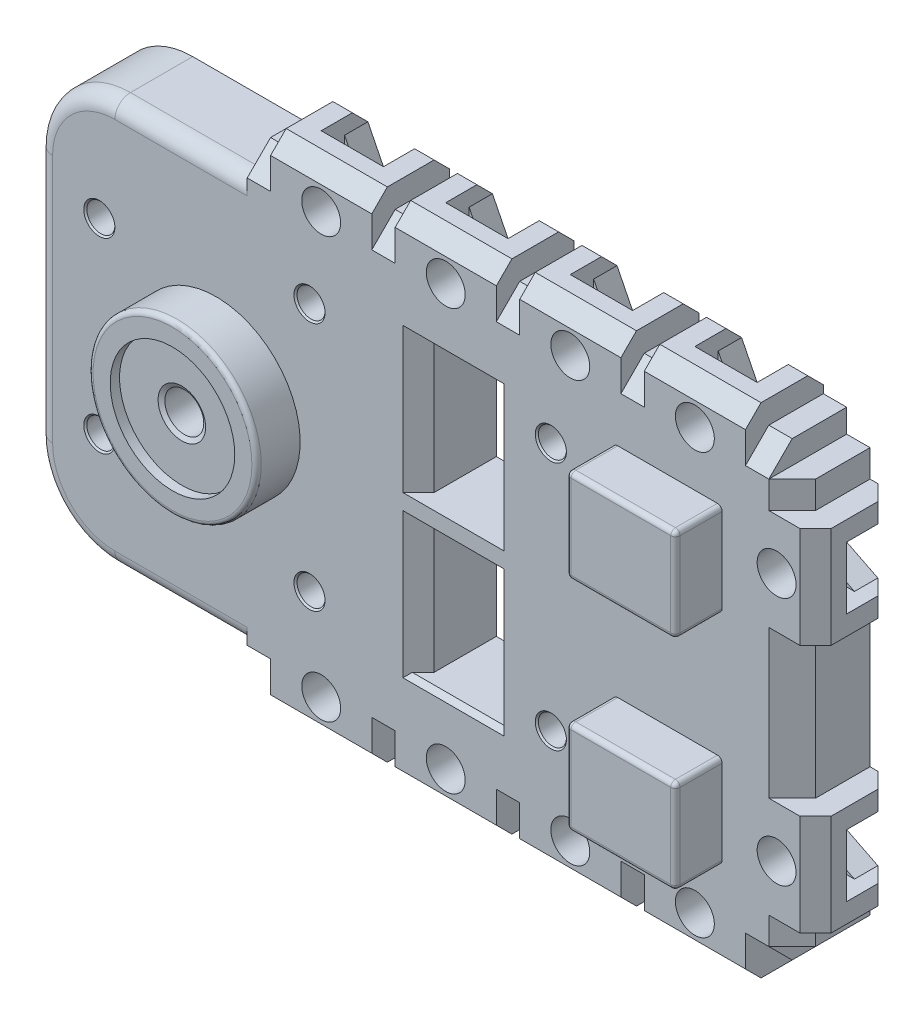
SolidWorks part; units mm, degrees
ref_plane "Front" through (0, 0, 0) normal (0, 0, 1) x (1, 0, 0)
ref_plane "Top" through (0, 0, 0) normal (0, 1, 0) x (1, 0, 0)
ref_plane "Right" through (0, 0, 0) normal (1, 0, 0) x (0, 0, -1)
sketch "Sketch1" plane through (0, 0, 0) normal (0, 0, 1) x (1, 0, 0)
  line L0 (12.75, 0) -> (38.5, 0) construction
  line L1 (37, -13) -> (35.5, -13)
  line L2 (37, -13) -> (37, -11.25)
  line L3 (37, 13) -> (35.5, 13)
  line L4 (-11.5, -13) -> (-11.5, 13)
  line L5 (37, -13) -> (-11.5, 13) construction
  line L6 (37, 13) -> (-11.5, -13) construction
  line L7 (37, -4.75) -> (38.5, -4.75)
  line L8 (38.5, -11.25) -> (38.5, -4.75)
  line L9 (37, -11.25) -> (38.5, -11.25)
  line L10 (37, -4.75) -> (37, 4.75)
  line L11 (2, 13) -> (-11.5, 13)
  line L12 (2, 13) -> (2, 14.5)
  line L13 (35.5, 13) -> (35.5, 14.5)
  line L14 (2, 14.5) -> (3.5, 14.5)
  line L15 (37, 11.25) -> (37, 13)
  line L16 (37, 11.25) -> (38.5, 11.25)
  line L17 (37, 4.75) -> (38.5, 4.75)
  line L18 (38.5, 11.25) -> (38.5, 4.75)
  line L19 (35.5, -13) -> (35.5, -14.5)
  line L20 (34, -14.5) -> (35.5, -14.5)
  line L21 (34, -14.5) -> (34, -16)
  line L22 (34, -16) -> (27.5, -16)
  line L23 (34, 14.5) -> (35.5, 14.5)
  line L24 (34, 14.5) -> (34, 16)
  line L25 (27.5, 14.5) -> (27.5, 16)
  line L26 (34, 16) -> (27.5, 16)
  line L27 (26, 14.5) -> (27.5, 14.5)
  line L28 (26, 14.5) -> (26, 16)
  line L29 (19.5, 14.5) -> (19.5, 16)
  line L30 (26, 16) -> (19.5, 16)
  line L31 (18, 14.5) -> (19.5, 14.5)
  line L32 (18, 14.5) -> (18, 16)
  line L33 (11.5, 14.5) -> (11.5, 16)
  line L34 (18, 16) -> (11.5, 16)
  line L35 (10, 14.5) -> (11.5, 14.5)
  line L36 (10, 14.5) -> (10, 16)
  line L37 (3.5, 14.5) -> (3.5, 16)
  line L38 (10, 16) -> (3.5, 16)
  line L39 (27.5, -14.5) -> (27.5, -16)
  line L40 (26, -14.5) -> (27.5, -14.5)
  line L41 (26, -14.5) -> (26, -16)
  line L42 (26, -16) -> (19.5, -16)
  line L43 (19.5, -14.5) -> (19.5, -16)
  line L44 (18, -14.5) -> (19.5, -14.5)
  line L45 (18, -14.5) -> (18, -16)
  line L46 (18, -16) -> (11.5, -16)
  line L47 (11.5, -14.5) -> (11.5, -16)
  line L48 (10, -14.5) -> (11.5, -14.5)
  line L49 (10, -14.5) -> (10, -16)
  line L50 (10, -16) -> (3.5, -16)
  line L51 (3.5, -14.5) -> (3.5, -16)
  line L52 (2, -14.5) -> (3.5, -14.5)
  line L53 (2, -13) -> (2, -14.5)
  line L54 (2, -13) -> (-11.5, -13)
  point P0 (12.75, 0)
  dimension "D1" = 48.5
  dimension "D2" = 26
  dimension "D3" = 11.5
  dimension "D4" = 1.5
  dimension "D5" = 33.5
  dimension "D6" = 1.5
  dimension "D7" = 1.5
  dimension "D8" = 6.5
  dimension "D9" = 22.5
  dimension "D10" = 1.5
  dimension "D11" = 6.5
  dimension "D12" = 1.5
  dimension "D13" = 1.5
extrude "Boss-Extrude1" add sketch "Sketch1" along normal mid plane 5
sketch "Sketch4" plane through (0, 0, 2.5) normal (0, 0, 1) x (1, 0, 0)
  line L0 (-11.5, 13) -> (-11.5, -13) construction
  line L1 (32.5, -10) -> (-11.5, -10)
  line L2 (32.5, -10) -> (32.5, 10)
  line L3 (32.5, 10) -> (-11.5, 10)
  line L4 (-11.5, -10) -> (-11.5, 10)
  line L5 (32.5, -10) -> (-11.5, 10) construction
  line L6 (32.5, 10) -> (-11.5, -10) construction
  point P0 (10.5, 0)
  dimension "D1" = 20
  dimension "D2" = 44
sketch "Sketch5" plane through (0, 0, 2.5) normal (0, 0, 1) x (1, 0, 0)
  line L1 (32.5, 10) -> (25.5, 10)
  line L2 (32.5, 10) -> (32.5, 4)
  line L3 (25.5, -10) -> (25.5, -4)
  line L4 (25.5, 10) -> (25.5, 4)
  line L5 (32.5, -10) -> (25.5, -10)
  line L6 (37, -4.75) -> (37, 4.75) construction
  line L7 (25.5, 4) -> (32.5, 4)
  line L8 (0, 0) -> (35.7232, 0) construction
  line L9 (32.5, -10) -> (32.5, -4)
  line L10 (25.5, -4) -> (32.5, -4)
  dimension "D2" = 4.5
  dimension "D1" = 7
  dimension "D3" = 20
  dimension "D4" = 8
extrude "Boss-Extrude3" add sketch "Sketch5" along normal blind 3
sketch "Sketch6" plane through (38.5, 0, 0) normal (1, 0, 0) x (0, 0, -1)
  line L0 (2.5, 4.75) -> (2.5, 11.25) construction
  line L1 (-0.5, 10) -> (2.5, 10)
  line L2 (-0.5, 10) -> (-0.5, 6)
  line L3 (-0.5, 6) -> (2.5, 6)
  line L4 (2.5, 10) -> (2.5, 6)
  line L5 (-0.5, 10) -> (2.5, 6) construction
  line L6 (-0.5, 6) -> (2.5, 10) construction
  line L7 (-2.5, 8) -> (1, 8) construction
  line L8 (-2.5, 4.75) -> (-2.5, 11.25) construction
  point P0 (1, 8)
  dimension "D1" = 4
  dimension "D2" = 2
extrude "Cut-Extrude3" cut sketch "Sketch6" against normal blind 1
sketch "Sketch7" plane through (0, 0, 0.5) normal (0, 0, -1) x (-1, 0, 0)
  line L0 (-37.5, 10) -> (-38.5, 10) construction
  line L1 (-37.1547, 10) -> (-38.3094, 8) construction
  line L2 (-38.3094, 8) -> (-37.1547, 6) construction
  line L3 (-37.1547, 6) -> (-34.8453, 6)
  line L6 (-34.8453, 6) -> (-33.6906, 8)
  line L7 (-33.6906, 8) -> (-34.8453, 10)
  line L8 (-34.8453, 10) -> (-37.1547, 10)
  line L9 (-37.5, 8) -> (-36, 8) construction
  line L10 (-37.5, 6) -> (-37.5, 10) construction
  line L11 (-38.5, 10) -> (-38.5, 6) construction
  line L12 (-37.1547, 10) -> (-38.5, 10)
  line L13 (-38.5, 10) -> (-38.5, 6)
  line L14 (-38.5, 6) -> (-37.1547, 6)
  circle A0 centre (-36, 8) radius 2 construction
  dimension "D1" = 2.5
extrude "Cut-Extrude4" cut sketch "Sketch7" along normal blind 1.5
sketch "Sketch8" plane through (0, 0, -2.5) normal (0, 0, -1) x (-1, 0, 0)
  line L0 (-37.5, 10) -> (-35.5, 9)
  line L1 (-35.5, 9) -> (-35.5, 7)
  line L2 (-35.5, 7) -> (-37.5, 6)
  line L3 (-34.8453, 6) -> (-38.5, 6) construction
  line L4 (-37.5, 6) -> (-38.5, 6) construction
  line L5 (-37.5, 8) -> (-35.5, 8) construction
  line L6 (-37.5, 6) -> (-37.5, 10) construction
  line L7 (-37, -4.75) -> (-37, 4.75) construction
  line L8 (-37.5, 10) -> (-37.5, 6)
  dimension "D1" = 2
  dimension "D2" = 1.5
extrude "Cut-Extrude5" cut sketch "Sketch8" against normal up to next
sketch "Sketch10" plane through (0, 16, 0) normal (0, 1, 0) x (1, 0, 0)
  line L0 (28.75, -0.5) -> (28.75, 2.5)
  line L1 (28.75, -0.5) -> (32.75, -0.5)
  line L2 (32.75, -0.5) -> (32.75, 2.5)
  line L3 (28.75, 2.5) -> (32.75, 2.5)
  line L4 (28.75, -0.5) -> (32.75, 2.5) construction
  line L5 (32.75, -0.5) -> (28.75, 2.5) construction
  line L6 (30.75, -2.5) -> (30.75, 1) construction
  line L7 (34, -2.5) -> (27.5, -2.5) construction
  line L8 (34, 2.5) -> (27.5, 2.5) construction
  point P0 (30.75, 1)
  dimension "D1" = 4
  dimension "D2" = 3
extrude "Cut-Extrude6" cut sketch "Sketch10" against normal blind 1
sketch "Sketch11" plane through (0, 0, 0.5) normal (0, 0, -1) x (-1, 0, 0)
  line L0 (-30.75, 16) -> (-30.75, 13.5) construction
  line L1 (-30.75, 15.8094) -> (-32.75, 14.6547) construction
  line L2 (-32.75, 14.6547) -> (-32.75, 12.3453)
  line L3 (-32.75, 12.3453) -> (-30.75, 11.1906)
  line L4 (-30.75, 11.1906) -> (-28.75, 12.3453)
  line L5 (-28.75, 12.3453) -> (-28.75, 14.6547)
  line L6 (-28.75, 14.6547) -> (-30.75, 15.8094) construction
  line L7 (-28.75, 16) -> (-32.75, 16) construction
  line L8 (-34, 16) -> (-32.75, 16) construction
  line L9 (-28.75, 14.6547) -> (-28.75, 16)
  line L10 (-28.75, 16) -> (-32.75, 16)
  line L11 (-32.75, 16) -> (-32.75, 14.6547)
  circle A0 centre (-30.75, 13.5) radius 2 construction
  dimension "D1" = 4
  dimension "D2" = 2.5
extrude "Cut-Extrude7" cut sketch "Sketch11" along normal blind 1.5
sketch "Sketch12" plane through (0, 0, -2.5) normal (0, 0, -1) x (-1, 0, 0)
  line L0 (-28.75, 15) -> (-29.75, 13)
  line L1 (-29.75, 13) -> (-31.75, 13)
  line L2 (-31.75, 13) -> (-32.75, 15)
  line L3 (-30.75, 15) -> (-30.75, 13) construction
  line L4 (-32.75, 15) -> (-28.75, 15) construction
  line L5 (-35.5, 14.5) -> (-34, 14.5) construction
  line L6 (-32.75, 15) -> (-28.75, 15)
  dimension "D1" = 1.5
  dimension "D2" = 2
extrude "Cut-Extrude8" cut sketch "Sketch12" against normal up to next
sketch "Sketch13" plane through (0, 0, 2.5) normal (0, 0, 1) x (1, 0, 0)
  circle A0 centre (36, 8) radius 1.25
  dimension "D1" = 2.5
extrude "Cut-Extrude9" cut sketch "Sketch13" against normal up to next
sketch "Sketch14" plane through (0, 0, 2.5) normal (0, 0, 1) x (1, 0, 0)
  circle A0 centre (30.75, 13.5) radius 1.25
  dimension "D1" = 2.5
extrude "Cut-Extrude10" cut sketch "Sketch14" against normal up to next
pattern_linear "LPattern1" count 4 spacing 8 along (-1, 0, 0) of "Cut-Extrude6", "Cut-Extrude7", "Cut-Extrude8", "Cut-Extrude10"
mirror "Mirror1" about plane through (0, 0, 0) normal (0, 1, 0) of "LPattern1", "Cut-Extrude10", "Cut-Extrude9", "Cut-Extrude8", "Cut-Extrude7", "Cut-Extrude6", "Cut-Extrude5", "Cut-Extrude4", "Cut-Extrude3"
fillet "Fillet1" radius 5 2 edges at (-11.5, -13, 0) (-11.5, 13, 0)
sketch "Sketch15" plane through (0, 0, 2.5) normal (0, 0, 1) x (1, 0, 0)
  line L0 (0, 0) -> (38.4863, 0) construction
  line L1 (38.5, 4.75) -> (38.5, 11.25) construction
  line L3 (-7.25, 9.25) -> (-7.25, 14.1999)
  line L4 (-7.25, 14.1999) -> (-13.5472, 14.1999)
  line L5 (-13.5472, 14.1999) -> (-13.5472, 7.5)
  line L6 (-13.5472, 7.5) -> (-9, 7.5)
  line L7 (-13.5472, -14.1999) -> (-13.5472, -7.5)
  line L8 (-7.25, -14.1999) -> (-13.5472, -14.1999)
  line L9 (-7.25, -9.25) -> (-7.25, -14.1999)
  line L10 (-13.5472, -7.5) -> (-9, -7.5)
  line L11 (-11.5, -10) -> (-11.5, 10) construction
  circle A0 centre (33, 10.4) radius 1.75
  circle A1 centre (33, -10.4) radius 1.75
  arc A2 (-9, 7.5) -> (-7.25, 9.25) centre (-9, 9.25) ccw
  circle A3 centre (33, -10.4) radius 1.75
  arc A4 (-9, -7.5) -> (-7.25, -9.25) centre (-9, -9.25) cw
  dimension "D1" = 20.8
  dimension "D2" = 5.5
  dimension "D3" = 3.5
  dimension "D4" = 18.5
  dimension "D5" = 2.5
sketch "Sketch2" plane through (0, 0, 2.5) normal (0, 0, 1) x (1, 0, 0)
  line L0 (0, 0) -> (23.4398, 0) construction
  line L1 (13, 9.5) -> (17.5, 9.5)
  line L2 (13, 9.5) -> (13, 0.5)
  line L3 (13, 0.5) -> (17.5, 0.5)
  line L4 (17.5, 9.5) -> (17.5, 0.5)
  line L5 (13, 9.5) -> (17.5, 0.5) construction
  line L6 (13, 0.5) -> (17.5, 9.5) construction
  line L7 (13, -9.5) -> (13, -0.5)
  line L8 (13, -9.5) -> (17.5, -9.5)
  line L9 (17.5, -9.5) -> (17.5, -0.5)
  line L10 (13, -0.5) -> (17.5, -0.5)
  point P0 (15.25, 5)
  dimension "D1" = 4.5
  dimension "D2" = 9
  dimension "D3" = 13
  dimension "D4" = 19
extrude "Cut-Extrude1" cut sketch "Sketch2" against normal through all
sketch "Sketch3" plane through (0, 0, 2.5) normal (0, 0, 1) x (1, 0, 0)
  circle A0 centre (0, 0) radius 5.4
  dimension "D1" = 10.8
extrude "Boss-Extrude4" add sketch "Sketch3" along normal blind 2.8
sketch "Sketch17" plane through (0, 0, 5.3) normal (0, 0, 1) x (1, 0, 0)
  circle A0 centre (0, 0) radius 4
  dimension "D1" = 8
extrude "Cut-Extrude13" cut sketch "Sketch17" against normal blind 0.6
hole_wizard "Ø1.6 (1.6) Diameter Hole1" positions "Sketch19" profile "Sketch18" hole size "Ø1.6" standard "ISO"
sketch "Sketch19" plane through (0, 0, -2.5) normal (0, 0, -1) x (-1, 0, 0)
  point P0 (-33, 10.4)
  point P3 (-33, -10.4)
  point P6 (9, 9.25)
  point P9 (9, -9.25)
sketch "Sketch18" plane through (33, 10.4, -2.5) normal (1, 0, 0) x (0, 1, 0)
  line L0 (0, 0) -> (0, 4.9807)
  line L1 (0, 4.9807) -> (0.8, 4.5)
  line L2 (0.8, 4.5) -> (0.8, 0.0577)
  line L3 (0.8, 0.0577) -> (0.9, 0)
  line L5 (0.9, 0) -> (0, 0)
  line L6 (-0.8, 0.0577) -> (-0.9, 0) construction
  line L10 (0, 4.9807) -> (-0.8, 4.5) construction
  line L11 (0, -6.35) -> (0, 107.95) construction
  dimension "Hole Dia." = 1.6
  dimension "Hole Depth" = 4.5
  dimension "Near C'Sink Dia." = 1.8
  dimension "Near C'Sink Angle" = 120
  dimension "Drill Angle" = 118
hole_wizard "M3 Tapped Hole1" positions "Sketch21" profile "Sketch22" tap size "M3" standard "ISO" end condition through all
sketch "Sketch21" plane through (0, 0, 4.7) normal (0, 0, 1) x (1, 0, 0)
  point P0 (0, 0)
sketch "Sketch22" plane through (0, 0, 4.7) normal (1, 0, 0) x (0, -1, 0)
  line L0 (0, 0) -> (0, 7.2)
  line L1 (0, 7.2) -> (1.25, 7.2)
  line L2 (1.25, 7.2) -> (1.25, 0.1588)
  line L3 (1.25, 0.1588) -> (1.525, 0)
  line L5 (1.525, 0) -> (0, 0)
  line L6 (-1.25, 0.1588) -> (-1.525, 0) construction
  line L11 (0, -6.35) -> (0, 107.95) construction
  dimension "Thru Tap Drill Dia." = 2.5
  dimension "Thru Tap Drill Depth" = 7.2
  dimension "Near C'Sink Dia." = 3.05
  dimension "Near C'Sink Angle" = 120
cosmetic thread "Hole Thread1" parameters "D2"=3
hole_wizard "Ø1.8 (1.8) Diameter Hole1" positions "Sketch24" profile "Sketch25" hole size "Ø1.8" standard "ISO" end condition through all
sketch "Sketch24" plane through (0, 0, 2.5) normal (0, 0, 1) x (1, 0, 0)
  line L0 (0, 0) -> (35.0384, 0) construction
  point P0 (6, 8)
  point P7 (21.5, 8)
  point P9 (-7.5, 6)
  point P14 (21.5, -8)
  point P15 (6, -8)
  point P16 (-7.5, -6)
  dimension "D1" = 16
  dimension "D2" = 6
  dimension "D3" = 15.5
  dimension "D4" = 12
  dimension "D5" = 7.5
sketch "Sketch25" plane through (6, 8, 2.5) normal (1, 0, 0) x (0, -1, 0)
  line L0 (0, 0) -> (0, 5)
  line L1 (0, 5) -> (0.9, 5)
  line L2 (0.9, 5) -> (0.9, 0.1)
  line L3 (0.9, 0.1) -> (1, 0)
  line L5 (1, 0) -> (0, 0)
  line L6 (-0.9, 0.1) -> (-1, 0) construction
  line L11 (0, -6.35) -> (0, 107.95) construction
  dimension "Thru Hole Dia." = 1.8
  dimension "Thru Hole Depth" = 5
  dimension "Near C'Sink Dia." = 2
  dimension "Near C'Sink Angle" = 90
fillet "Fillet2" radius 1 5 edges at (-2.25, 13, 2.5) (-10.0355, 11.5355, 2.5) (-11.5, 0, 2.5) (-10.0355, -11.5355, 2.5) (-2.25, -13, 2.5)
chamfer "Chamfer1" distance 1 angle 45 30 edges at (4.125, -16, -2.5) (9.375, -16, -2.5) (12.125, -16, -2.5) (17.375, -16, -2.5) (20.125, -16, -2.5) (25.375, -16, -2.5) (28.125, -16, -2.5) (33.375, -16, -2.5) (4.125, 16, -2.5) (9.375, 16, -2.5) (12.125, 16, -2.5) (17.375, 16, -2.5) (20.125, 16, -2.5) (25.375, 16, -2.5) (28.125, 16, -2.5) (33.375, 16, -2.5) (38.5, -10.625, -2.5) (38.5, -5.375, -2.5) (38.5, 5.375, -2.5) (38.5, 10.625, -2.5) (6.75, 16, 2.5) (14.75, 16, 2.5) (22.75, 16, 2.5) (30.75, 16, 2.5) (38.5, 8, 2.5) (38.5, -8, 2.5) (30.75, -16, 2.5) (22.75, -16, 2.5) (14.75, -16, 2.5) (6.75, -16, 2.5)
chamfer "Chamfer2" distance 1.5 angle 45 13 edges at (2.75, 14.5, 2.5) (10.75, 14.5, 2.5) (18.75, 14.5, 2.5) (26.75, 14.5, 2.5) (34.75, 14.5, 2.5) (37, 12.125, 2.5) (2.75, -14.5, 2.5) (10.75, -14.5, 2.5) (18.75, -14.5, 2.5) (26.75, -14.5, 2.5) (37, -12.125, 2.5) (34.75, -14.5, 2.5) (37, 0, 2.5)
chamfer "Chamfer3" distance 1 angle 45 4 edges at (13, 5, 2.5) (17.5, 5, 2.5) (17.5, -5, 2.5) (13, -5, 2.5)
chamfer "Chamfer4" distance 0.3 angle 45 2 edges at (15.25, 9.5, 2.5) (15.25, -9.5, 2.5)
fillet "Fillet3" radius 0.3 17 edges at (29, 4, 5.5) (25.5, 7, 5.5) (29, 10, 5.5) (32.5, 7, 5.5) (25.5, -7, 5.5) (29, -4, 5.5) (32.5, -7, 5.5) (29, -10, 5.5) (5.4, 0, 5.3) (25.5, 10, 4) (32.5, 10, 4) (32.5, 4, 4) (25.5, 4, 4) (25.5, -4, 4) (32.5, -4, 4) (32.5, -10, 4) (25.5, -10, 4)
